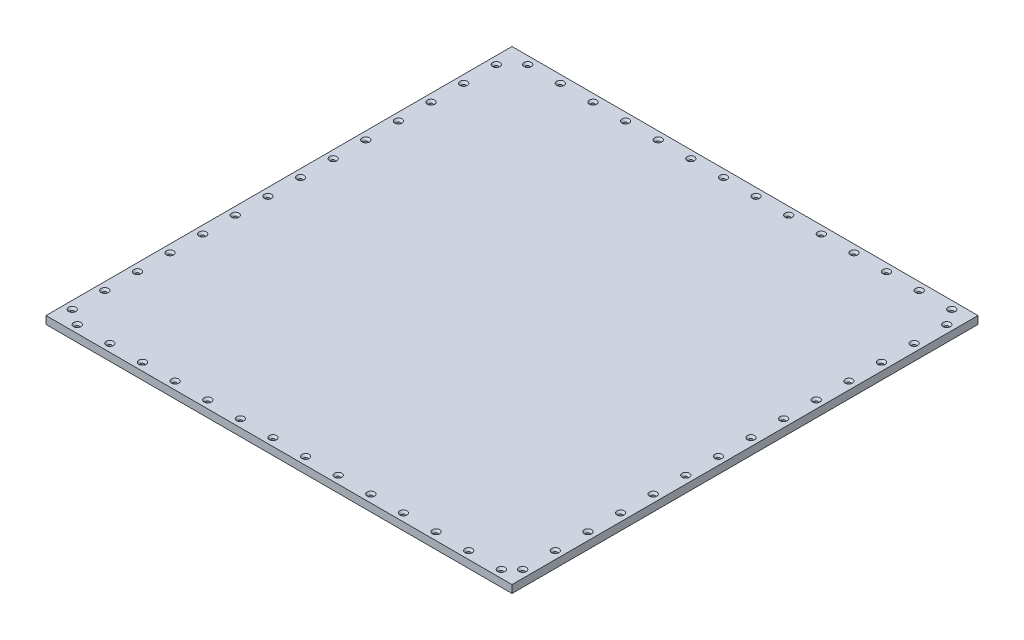
SolidWorks part; units mm, degrees
ref_plane "Płaszczyzna przednia" through (0, 0, 0) normal (0, 0, 1) x (1, 0, 0)
ref_plane "Płaszczyzna górna" through (0, 0, 0) normal (0, 1, 0) x (1, 0, 0)
ref_plane "Płaszczyzna prawa" through (0, 0, 0) normal (1, 0, 0) x (0, 0, -1)
sketch "Sketch1" plane through (0, 0, 0) normal (0, 1, 0) x (1, 0, 0)
  line L1 (0, 0) -> (600, 0)
  line L2 (0, 0) -> (0, 600)
  line L3 (0, 600) -> (600, 600)
  line L4 (600, 0) -> (600, 600)
  line L5 (0, 0) -> (600, 600) construction
  line L6 (0, 600) -> (600, 0) construction
  point P4 (300, 300)
  dimension "D1" = 600
  dimension "D2" = 600
extrude "Boss-Extrude1" add sketch "Sketch1" along normal blind 10
hole_wizard "CSK for M4 Flat Head Machine Screw1" positions "Sketch2" profile "Sketch3" countersink size "M4" standard "ANSI Metric" end condition through all
sketch "Sketch2" plane through (0, 10, 0) normal (0, 1, 0) x (1, 0, 0)
  line L0 (600, 600) -> (0, 600) construction
  line L1 (0, 600) -> (0, 0) construction
  point P0 (10, 569.75)
  point P2 (30.25, 590)
  point P20 (72.25, 590)
  point P21 (114.25, 590)
  point P22 (156.25, 590)
  point P23 (198.25, 590)
  point P24 (240.25, 590)
  point P25 (282.25, 590)
  point P26 (324.25, 590)
  point P27 (366.25, 590)
  point P28 (408.25, 590)
  point P29 (450.25, 590)
  point P30 (492.25, 590)
  point P31 (534.25, 590)
  point P32 (576.25, 590)
  point P33 (72.25, 10)
  point P34 (114.25, 10)
  point P35 (156.25, 10)
  point P36 (198.25, 10)
  point P37 (240.25, 10)
  point P38 (282.25, 10)
  point P39 (324.25, 10)
  point P40 (366.25, 10)
  point P41 (408.25, 10)
  point P42 (450.25, 10)
  point P43 (492.25, 10)
  point P44 (534.25, 10)
  point P45 (576.25, 10)
  point P46 (30.25, 10)
  point P53 (590, 569.75)
  point P54 (590, 527.75)
  point P55 (590, 485.75)
  point P56 (590, 443.75)
  point P57 (590, 401.75)
  point P58 (590, 359.75)
  point P59 (590, 317.75)
  point P60 (590, 275.75)
  point P61 (590, 233.75)
  point P62 (590, 191.75)
  point P63 (590, 149.75)
  point P64 (590, 107.75)
  point P65 (590, 65.75)
  point P66 (590, 23.75)
  point P67 (10, 527.75)
  point P68 (10, 485.75)
  point P69 (10, 443.75)
  point P70 (10, 401.75)
  point P71 (10, 359.75)
  point P72 (10, 317.75)
  point P73 (10, 275.75)
  point P74 (10, 233.75)
  point P75 (10, 191.75)
  point P76 (10, 149.75)
  point P77 (10, 107.75)
  point P78 (10, 65.75)
  point P79 (10, 23.75)
  dimension "D1" = 30.25
  dimension "D2" = 10
  dimension "D3" = 10
  dimension "D4" = 30.25
  dimension "D5" = 14
  dimension "D6" = 2
  dimension "D7" = 2
  dimension "D8" = 14
sketch "Sketch3" plane through (10, 10, -569.75) normal (1, 0, 0) x (0, 0, 1)
  line L0 (0, 0) -> (0, 10)
  line L1 (0, 10) -> (2.15, 10)
  line L2 (2.15, 10) -> (2.15, 2.55)
  line L3 (2.15, 2.55) -> (4.7, 0)
  line L5 (4.7, 0) -> (0, 0)
  line L6 (-2.15, 2.55) -> (-4.7, 0) construction
  line L11 (0, -6.35) -> (0, 107.95) construction
  dimension "Thru Hole Dia." = 4.3
  dimension "Thru Hole Depth" = 10
  dimension "Near C'Sink Dia." = 9.4
  dimension "Near C'Sink Angle" = 90
